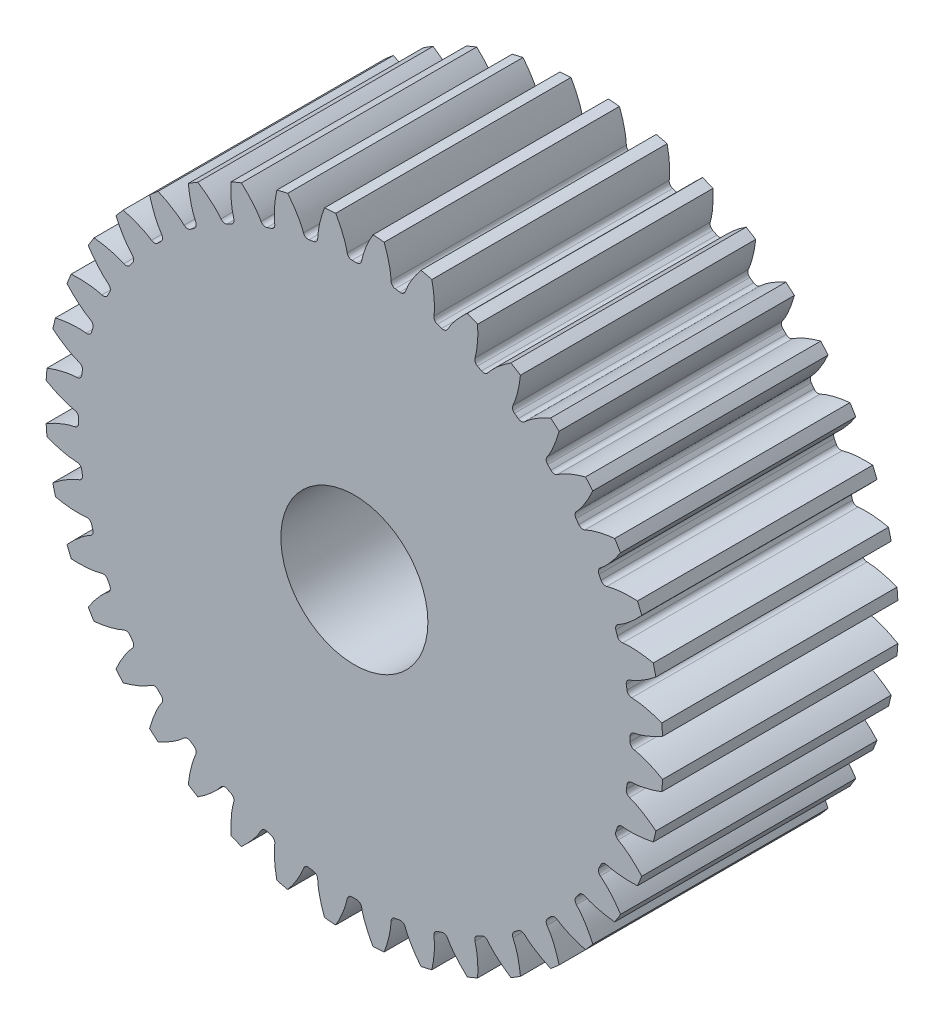
SolidWorks part; units mm, degrees
material "Plain Carbon Steel"
ref_plane "Front Plane" through (0, 0, 0) normal (0, 0, 1) x (1, 0, 0)
ref_plane "Top Plane" through (0, 0, 0) normal (0, 1, 0) x (1, 0, 0)
ref_plane "Right Plane" through (0, 0, 0) normal (1, 0, 0) x (0, 0, -1)
sketch "Sketch1" plane through (0, 0, 0) normal (0, 0, 1) x (1, 0, 0)
  line L0 (0, 0) -> (0, 15.875) construction
  line L1 (-5.1021, 17.732) -> (5.1021, 14.018) construction
  circle A0 centre (0, 0) radius 14.8828 construction
  circle A1 centre (0, 0) radius 16.6687 construction
  circle A2 centre (0, 0) radius 15.875 construction
  circle A3 centre (0, 0) radius 14.9176 construction
  point P8 (406.4, 0)
  point P13 (508, 0)
  dimension "OD | Outside Diameter" = 33.3375
  dimension "Root Diameter" = 29.7656
  dimension "Gear Pitch Diameter" = 31.75
  dimension "Base Diameter" = 29.8352
  dimension "Pressure Angle" = 20
  dimension "Number of Teeth" = 1016
  dimension "Gear Pitch | Diametral Pitch" = 812.8
sketch "Sketch2" plane through (0, 0, 0) normal (1, 0, 0) x (0, 0, -1)
  line L0 (-6.35, 0) -> (6.35, 0) construction
  point P2 (10.3187, 0)
  point P5 (18.6531, 0)
  point P6 (-10.3187, 0)
  dimension "Length" = 12.7
  dimension "D1" = 16.6687
  dimension "D2" = 25.0031
  dimension "D3" = 16.6687
sketch "Sketch3" plane through (0, 0, 0) normal (0, 0, 1) x (1, 0, 0)
  circle A0 centre (0, 0) radius 16.6687
  circle A1 centre (0, 0) radius 16.6687 construction
extrude "Boss-Extrude1" add sketch "Sketch3" against normal up to vertex (6.35 mm away) and the other way up to vertex (6.35 mm away) up to point (0, 0, -6.35) other way up to point (0, 0, 6.35)
sketch "Sketch4" plane through (0, 0, 0) normal (0, 0, 1) x (1, 0, 0)
  line L0 (0, 0) -> (14.8784, 0.3626) construction
  line L2 (0, 0) -> (14.8784, -0.3626) construction
  line L4 (14.8784, 0.3626) -> (14.9132, 0.3634)
  line L5 (14.9132, -0.3634) -> (14.8784, -0.3626)
  arc A0 (14.8784, 0.3626) -> (14.8784, -0.3626) centre (0, 0) cw
  arc A3 (16.6383, 1.0067) -> (16.6383, -1.0067) centre (0, 0) cw
  circle A4 centre (0, 0) radius 16.6687 construction
  spline S0 degree 4 poles (14.9132, 0.3634) (14.9159, 0.3635) (14.9236, 0.3639) (14.9381, 0.3649) (14.9618, 0.3671) (14.9919, 0.3706) (15.0308, 0.376) (15.0766, 0.3835) (15.1268, 0.3928) (15.1814, 0.4042) (15.2358, 0.4166) (15.29, 0.4301) (15.3439, 0.4444) (15.4091, 0.4628) (15.4872, 0.4863) (15.5783, 0.516) (15.6814, 0.5524) (15.7862, 0.5921) (15.8891, 0.6335) (15.9927, 0.678) (16.0929, 0.7228) (16.1965, 0.7721) (16.2921, 0.8189) (16.3988, 0.8743) (16.4848, 0.9199) (16.5978, 0.9832) (16.6645, 1.0215) (16.7423, 1.0675) (16.7768, 1.0885) (16.798, 1.1014) knots 0 0 0 0 0 0.005377 0.015084 0.028532 0.04661 0.064855 0.092111 0.119476 0.146842 0.174209 0.201575 0.228941 0.256307 0.307035 0.361767 0.4165 0.471232 0.525964 0.580697 0.635429 0.690161 0.744894 0.799626 0.854358 0.909091 0.954545 1 1 1 1 1 construction
  spline S1 degree 4 poles (14.9132, 0.3634) (14.9159, 0.3635) (14.9236, 0.3639) (14.9381, 0.3649) (14.9618, 0.3671) (14.9919, 0.3706) (15.0308, 0.376) (15.0766, 0.3835) (15.1268, 0.3928) (15.1814, 0.4042) (15.2358, 0.4166) (15.29, 0.4301) (15.3439, 0.4444) (15.4091, 0.4628) (15.4872, 0.4863) (15.5783, 0.516) (15.6814, 0.5524) (15.7862, 0.5921) (15.8891, 0.6335) (15.9927, 0.678) (16.0929, 0.7228) (16.1965, 0.7721) (16.2921, 0.8189) (16.3988, 0.8743) (16.4848, 0.9199) (16.5733, 0.9695) (16.6163, 0.994) (16.6383, 1.0067) knots 0 0 0 0 0 0.005377 0.015084 0.028532 0.04661 0.064855 0.092111 0.119476 0.146842 0.174209 0.201575 0.228941 0.256307 0.307035 0.361767 0.4165 0.471232 0.525964 0.580697 0.635429 0.690161 0.744894 0.799626 0.854358 0.909091 0.909091 0.909091 0.909091 0.909091
  spline S2 degree 4 poles (14.9132, -0.3634) (14.9159, -0.3635) (14.9236, -0.3639) (14.9381, -0.3649) (14.9618, -0.3671) (14.9919, -0.3706) (15.0308, -0.376) (15.0766, -0.3835) (15.1268, -0.3928) (15.1814, -0.4042) (15.2358, -0.4166) (15.29, -0.4301) (15.3439, -0.4444) (15.4091, -0.4628) (15.4872, -0.4863) (15.5783, -0.516) (15.6814, -0.5524) (15.7862, -0.5921) (15.8891, -0.6335) (15.9927, -0.678) (16.0929, -0.7228) (16.1965, -0.7721) (16.2921, -0.8189) (16.3988, -0.8743) (16.4848, -0.9199) (16.5978, -0.9832) (16.6645, -1.0215) (16.7423, -1.0675) (16.7768, -1.0885) (16.798, -1.1014) knots 0 0 0 0 0 0.005377 0.015084 0.028532 0.04661 0.064855 0.092111 0.119476 0.146842 0.174209 0.201575 0.228941 0.256307 0.307035 0.361767 0.4165 0.471232 0.525964 0.580697 0.635429 0.690161 0.744894 0.799626 0.854358 0.909091 0.954545 1 1 1 1 1 construction
  spline S3 degree 4 poles (14.9132, -0.3634) (14.9159, -0.3635) (14.9236, -0.3639) (14.9381, -0.3649) (14.9618, -0.3671) (14.9919, -0.3706) (15.0308, -0.376) (15.0766, -0.3835) (15.1268, -0.3928) (15.1814, -0.4042) (15.2358, -0.4166) (15.29, -0.4301) (15.3439, -0.4444) (15.4091, -0.4628) (15.4872, -0.4863) (15.5783, -0.516) (15.6814, -0.5524) (15.7862, -0.5921) (15.8891, -0.6335) (15.9927, -0.678) (16.0929, -0.7228) (16.1965, -0.7721) (16.2921, -0.8189) (16.3988, -0.8743) (16.4848, -0.9199) (16.5733, -0.9695) (16.6163, -0.994) (16.6383, -1.0067) knots 0 0 0 0 0 0.005377 0.015084 0.028532 0.04661 0.064855 0.092111 0.119476 0.146842 0.174209 0.201575 0.228941 0.256307 0.307035 0.361767 0.4165 0.471232 0.525964 0.580697 0.635429 0.690161 0.744894 0.799626 0.854358 0.909091 0.909091 0.909091 0.909091 0.909091
  dimension "D1" = 29.7656
extrude "Cut-Extrude1" cut sketch "Sketch4" against normal through all both and the other way through all
fillet "Fillet1" radius 0.2663 2 edges at (14.8784, -0.3626, 0) (14.8784, 0.3626, 0)
pattern_circular "CirPattern1" count 40 over 360 about axis through (0, 0, 6.35) along (0, 0, -1) of "Cut-Extrude1", "Fillet1"
sketch "Sketch5" plane through (0, 0, 6.35) normal (0, 0, 1) x (1, 0, 0)
  point P0 (0, 0)
hole_wizard "5/16 (0.3125) Dowel Hole1" positions "Sketch5" profile "Sketch6" hole size "5/16" standard "ANSI Inch" end condition through all
sketch "Sketch6" plane through (0, 0, 6.35) normal (1, 0, 0) x (0, -1, 0)
  line L0 (0, 0) -> (0, 12.7)
  line L1 (0, 12.7) -> (3.9687, 12.7)
  line L2 (3.9687, 12.7) -> (3.9687, 0)
  line L5 (3.9687, 0) -> (0, 0)
  line L11 (0, -6.35) -> (0, 107.95) construction
  dimension "Thru Hole Dia." = 7.9375
  dimension "Thru Hole Depth" = 12.7
equation "\"Root Diameter@Sketch1\"=\"Root Diameter\""
equation "\"OD | Outside Diameter@Sketch1\"=\"Outside Diameter\""
equation "\"D1@CirPattern1\"=\"Number of Teeth\""
equation "\"Diametral Pitch\"=32"
equation "\"Number of Teeth\"= 40"
equation "\"Pressure Angle\"=20"
equation "\"Pitch Diameter\"= \"Number of Teeth\" / \"Diametral Pitch\""
equation "\"Base Diameter\"= \"Pitch Diameter\" * cos ( \"Pressure Angle\" )"
equation "\"Outside Diameter\"= ( \"Number of Teeth\" + 2 ) / \"Diametral Pitch\""
equation "\"Dedendum\"= 1.25 / \"Diametral Pitch\""
equation "\"Root Diameter\"= \"Pitch Diameter\" - ( 2 * \"Dedendum\" )"
equation "\"Pitch Angle\"= 360deg / \"Number of Teeth\""
equation "\"Alpha\"= sqr ( \"Pitch Diameter\" ^ 2 - \"Base Diameter\" ^ 2 ) / \"Base Diameter\" * 180 / PI - \"Pressure Angle\""
equation "\"Beta\"= ( \"Pitch Angle\" / 4 - \"Alpha\" )"
equation "\"Phi\"= sqr ( ( \"Outside Diameter\" / 2 ) ^ 2 - ( \"Base Diameter\" / 2 ) ^ 2 ) / ( \"Base Diameter\" / 2 )"
equation "\"Addendum\"= 1 / \"Diametral Pitch\""
equation "\"WorkingDepth\"= 2 / \"Diametral Pitch\""
equation "\"WholeDepth\"= 2.25 / \"Diametral Pitch\""
equation "\"Clearance\"= 0.25 / \"Diametral Pitch\""
equation "\"ToothThickness\"= ( pi * 2 ) / \"Diametral Pitch\""
equation "\"CircularPitch\"= pi / \"Diametral Pitch\""
equation "\"Number of Teeth@Sketch1\"=\"Number of Teeth\""
equation "\"Gear Pitch | Diametral Pitch@Sketch1\"=\"Diametral Pitch\""
equation "\"Pressure Angle@Sketch1\"=\"Pressure Angle\""
equation "\"Gear Pitch Diameter@Sketch1\"=\"Pitch Diameter\""
equation "\"Base Diameter@Sketch1\"=\"Base Diameter\""
equation "\"Fillet\"= \"Clearance\" * cos ( \"Pressure Angle\" ) * tan ( ( 90 + \"Pressure Angle\" ) / 2 )"
equation "\"D1@Fillet1\"=\"Fillet\""
equation "\"D1@Sketch4\"=if( \"Base Diameter\">\"Root Diameter\",\"Root Diameter\",\"Base Diameter\"-.00001)"
equation "\"D1@Sketch2\"=\"OD | Outside Diameter@Sketch1\"*2*0.5*0.5"
equation "\"D2@Sketch2\"=\"D1@Sketch2\"*1.5"
equation "\"D3@Sketch2\"=\"D1@Sketch2\""
equation "\"Length\"= .5in"
equation "\"Length@Sketch2\"= \"Length\""
